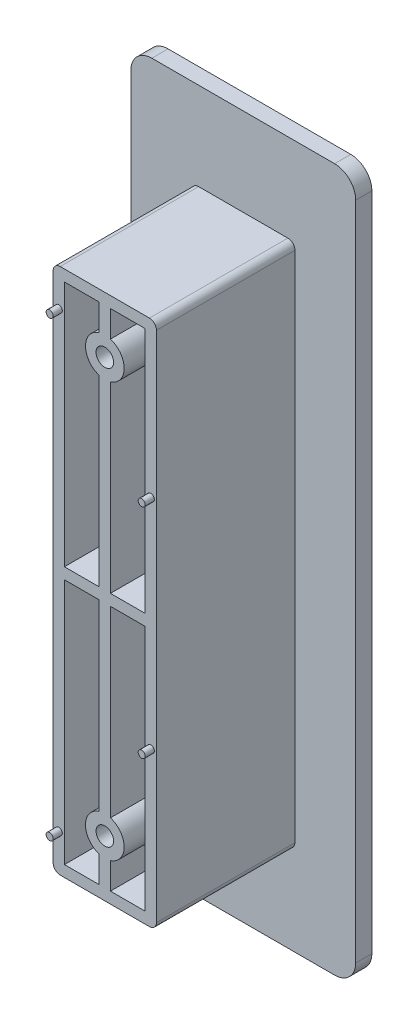
SolidWorks part; units mm, degrees
note: The reader was unsure of these and kept them because the rebuilt part matched: shared geometry of "스케치1<5>".
ref_plane "정면" through (0, 0, 0) normal (1, 0, 0) x (0, 1, 0)
ref_plane "윗면" through (0, 0, 0) normal (0, 0, 1) x (0, 1, 0)
ref_plane "우측면" through (0, 0, 0) normal (0, 1, 0) x (-1, 0, 0)
sketch "스케치1" plane through (0, 0, 0) normal (0, 0, 1) x (0, 1, 0)
  line L1 (-47, 16) -> (47, 16)
  line L2 (-50, 13) -> (-50, -13)
  line L3 (-47, -16) -> (47, -16)
  line L4 (50, 13) -> (50, -13)
  line L5 (-50, 16) -> (50, -16) construction
  line L6 (-50, -16) -> (50, 16) construction
  line L7 (-36.5, 7.35) -> (36.5, 7.35)
  line L8 (-37.5, 6.35) -> (-37.5, -6.35)
  line L9 (-36.5, -7.35) -> (36.5, -7.35)
  line L10 (37.5, 6.35) -> (37.5, -6.35)
  line L11 (-37.5, 7.35) -> (37.5, -7.35) construction
  line L12 (-37.5, -7.35) -> (37.5, 7.35) construction
  arc A0 (47, 16) -> (50, 13) centre (47, 13) cw
  arc A1 (47, -16) -> (50, -13) centre (47, -13) ccw
  arc A2 (-50, -13) -> (-47, -16) centre (-47, -13) ccw
  arc A3 (-47, 16) -> (-50, 13) centre (-47, 13) ccw
  arc A4 (36.5, 7.35) -> (37.5, 6.35) centre (36.5, 6.35) cw
  arc A5 (36.5, -7.35) -> (37.5, -6.35) centre (36.5, -6.35) ccw
  arc A6 (-37.5, -6.35) -> (-36.5, -7.35) centre (-36.5, -6.35) ccw
  arc A7 (-36.5, 7.35) -> (-37.5, 6.35) centre (-36.5, 6.35) ccw
  point P0 (0, 0)
  point P18 (0, 0)
  dimension "D3" = 3
  dimension "D6" = 1
  dimension "D1" = 32
  dimension "D2" = 100
  dimension "D4" = 14.7
  dimension "D5" = 75
extrude "보스-돌출2" add sketch "스케치1" along normal blind 22 contours L7 A7 L8 A6 L9 A5 L10 A4
extrude "보스-돌출3" add sketch "스케치1<5>" along normal blind 2.3
sketch "스케치1<5>" plane through (0, 0, 0) normal (0, 0, 1) x (0, 1, 0) same geometry as "스케치1"
shell "쉘1" thickness 1.6
sketch "스케치3" plane through (0, 0, 1.6) normal (0, 0, 1) x (1, 0, 0)
  line L0 (0, 42.7387) -> (0, -54.8443) construction
  line L1 (-20.7419, 0) -> (24.4326, 0) construction
  line L2 (0.8, 35.9) -> (0.8, 0.8)
  line L3 (5.75, 35.9) -> (-5.75, 35.9) construction
  line L4 (0.8, 0.8) -> (5.75, 0.8)
  line L5 (5.75, 35.9) -> (5.75, -35.9) construction
  line L6 (-0.8, 35.9) -> (-0.8, 0.8)
  line L7 (0.8, -0.8) -> (5.75, -0.8)
  line L8 (0.8, -35.9) -> (0.8, -0.8)
  line L9 (-0.8, -35.9) -> (-0.8, -0.8)
  line L10 (-0.8, 0.8) -> (-5.75, 0.8)
  line L11 (-0.8, -0.8) -> (-5.75, -0.8)
  line L12 (-5.75, -0.8) -> (-5.75, 0.8)
  line L13 (5.75, -0.8) -> (5.75, 0.8)
  line L14 (0.8, 35.9) -> (-0.8, 35.9)
  line L15 (0.8, -35.9) -> (-0.8, -35.9)
  dimension "D1" = 0.8
  dimension "D2" = 0.8
extrude "보스-돌출4" add sketch "스케치3" along normal up to surface (20.4 mm away) up to face at (0, 0, 22)
sketch "스케치4" plane through (0, 0, 22) normal (0, 0, 1) x (1, 0, 0)
  line L0 (-6.35, 37.5) -> (6.35, 37.5) construction
  line L1 (-6.35, -37.5) -> (6.35, -37.5) construction
  circle A0 centre (0, 29.5) radius 2.75
  circle A1 centre (0, -29.5) radius 2.75
  circle A2 centre (0, 29.5) radius 1.25
  circle A3 centre (0, -29.5) radius 1.25
  line M4 (0.8, -35.9) -> (0.8, -0.8)
  line M9 (0.8, 0.8) -> (0.8, 35.9)
  line M12 (-0.8, 35.9) -> (-0.8, 0.8)
  line M26 (-0.8, -0.8) -> (-0.8, -35.9)
  dimension "D1" = 5.5
  dimension "D2" = 5.5
  dimension "D5" = 2.5
  dimension "D6" = 2.5
  dimension "D3" = 8
  dimension "D4" = 8
extrude "보스-돌출5" add sketch "스케치4" against normal up to body contours A2 A0 M12 | A2 A0 M12 M9 | A2 A0 M9 M12 | A2 A0 M9 | A3 A1 M26 | A3 A1 M4 M26 | A3 A1 M4 | A3 A1 M26 M4
sketch "스케치5" plane through (0, 0, 22) normal (0, 0, 1) x (1, 0, 0)
  circle A0 centre (0, -29.5) radius 1.25
  circle A1 centre (0, 29.5) radius 1.25
extrude "컷-돌출1" cut sketch "스케치5" along direction (0, 0, 1) on the side against the normal up to next (22 mm away)
sketch "스케치6" plane through (0, 0, 22) normal (0, 0, 1) x (1, 0, 0)
  line L0 (-6.35, -37.5) -> (6.35, -37.5) construction
  line L1 (7.35, -36.5) -> (7.35, 36.5) construction
  line L4 (-7.35, -36.5) -> (-7.35, 36.5) construction
  line L5 (-19.3116, 0) -> (24.1806, 0) construction
  circle A0 centre (-6.55, -32.2) radius 0.5
  circle A1 centre (6.55, -15.5) radius 0.5
  circle A2 centre (-6.55, 32.2) radius 0.5
  circle A3 centre (6.55, 15.5) radius 0.5
  dimension "D3" = 1
  dimension "D4" = 1
  dimension "D1" = 22
  dimension "D2" = 5.3
  dimension "D5" = 0.8
  dimension "D6" = 0.8
extrude "보스-돌출6" add sketch "스케치6" along normal blind 1.3
